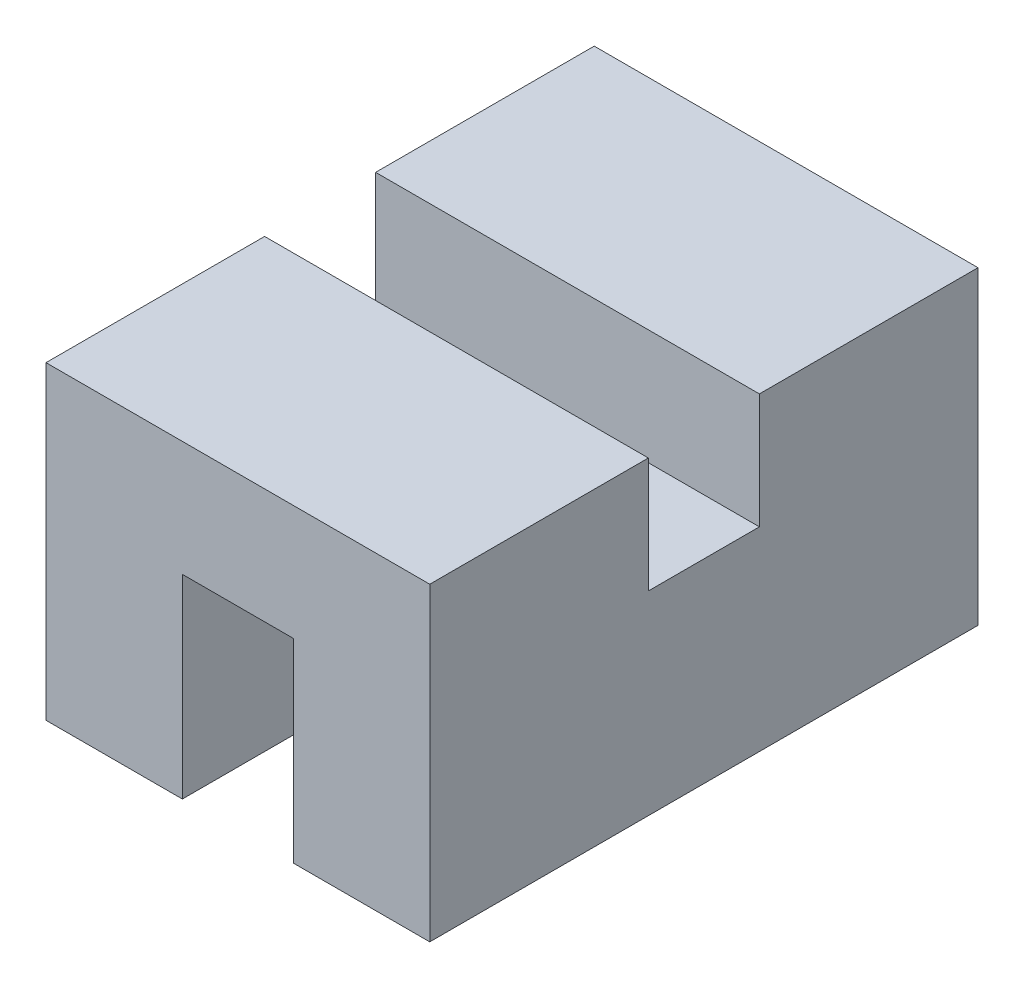
SolidWorks part; units mm, degrees
ref_plane "Front Plane" through (0, 0, 0) normal (0, 0, 1) x (1, 0, 0)
ref_plane "Top Plane" through (0, 0, 0) normal (0, 1, 0) x (1, 0, 0)
ref_plane "Right Plane" through (0, 0, 0) normal (1, 0, 0) x (0, 0, -1)
sketch "Sketch1" plane through (0, 0, 0) normal (0, 1, 0) x (1, 0, 0)
  line L0 (0, 0) -> (0, 40)
  line L1 (0, 40) -> (28, 40)
  line L2 (28, 40) -> (28, 0)
  line L3 (28, 0) -> (0, 0)
  dimension "D1" = 40
  dimension "D2" = 28
extrude "Boss-Extrude1" add sketch "Sketch1" along normal blind 5.8
sketch "Sketch2" plane through (0, 5.8, 0) normal (0, 1, 0) x (1, 0, 0)
  line L0 (28, 0) -> (28, 40) construction
  line L1 (0, 0) -> (28, 0)
  line L2 (0, 0) -> (0, 15.95)
  line L3 (0, 15.95) -> (28, 15.95)
  line L4 (28, 0) -> (28, 15.95)
  line L5 (28, 20) -> (0, 20) construction
  line L6 (0, 40) -> (28, 40)
  line L7 (0, 40) -> (0, 24.05)
  line L8 (0, 24.05) -> (28, 24.05)
  line L9 (28, 40) -> (28, 24.05)
  line L10 (0, 40) -> (0, 0) construction
  line L11 (28, 24.05) -> (28, 20) construction
  line L12 (28, 20) -> (28, 15.95) construction
  dimension "D1" = 8.1
extrude "Boss-Extrude2" add sketch "Sketch2" along normal blind 8.4
sketch "Sketch3" plane through (0, 0, 0) normal (0, -1, 0) x (1, 0, 0)
  line L0 (28, -40) -> (0, -40) construction
  line L1 (0, 0) -> (9.95, 0)
  line L2 (0, 0) -> (0, -40)
  line L3 (0, -40) -> (9.95, -40)
  line L4 (9.95, 0) -> (9.95, -40)
  line L5 (0, 0) -> (28, 0) construction
  line L7 (18.05, 0) -> (18.05, -40)
  line L10 (18.05, 0) -> (28, 0)
  line L20 (18.05, -40) -> (28, -40)
  line L22 (28, 0) -> (28, -40)
  line L23 (28, 0) -> (28, -40) construction
  dimension "D1" = 8.1
extrude "Boss-Extrude3" add sketch "Sketch3" along normal blind 8.4
sketch "Sketch4" plane through (0, 0, 0) normal (0, -1, 0) x (1, 0, 0)
  line L1 (9.95, 0) -> (18.05, 0)
  line L2 (9.95, 0) -> (9.95, -40)
  line L3 (9.95, -40) -> (18.05, -40)
  line L4 (18.05, 0) -> (18.05, -40)
extrude "Cut-Extrude1" cut sketch "Sketch4" against normal up to surface (5.8 mm away) up to face at (14, 5.8, -20)
equation "\"8mm hole\" = 8.4mm"
equation "\"22mm hole\"= 23mm"
equation "\"15mm hole\"= 15.8mm"
equation "\"bed height offset\"= 3mm"
equation "\"D1@Boss-Extrude1\"= 2.80mm + \"bed height offset\""
equation "\"D1@Boss-Extrude2\"= \"8mm hole\""
equation "\"D1@Boss-Extrude3\"= \"8mm hole\""
